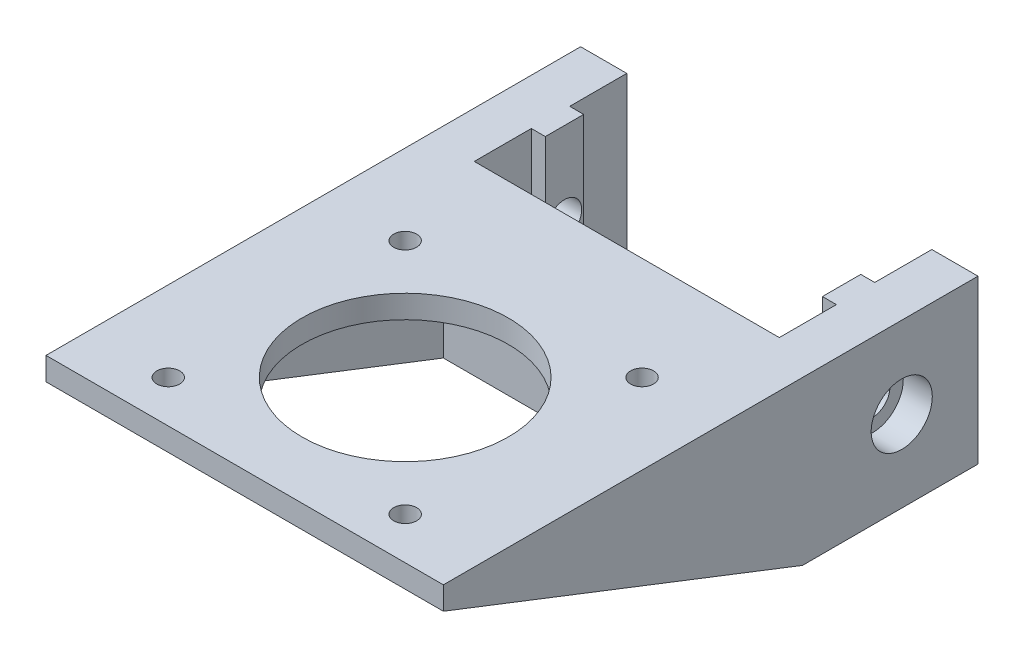
SolidWorks part; units mm, degrees
material "ABS"
ref_plane "Front Plane" through (0, 0, 0) normal (0, 0, 1) x (1, 0, 0)
ref_plane "Top Plane" through (0, 0, 0) normal (0, 1, 0) x (1, 0, 0)
ref_plane "Right Plane" through (0, 0, 0) normal (1, 0, 0) x (0, 0, -1)
sketch "Sketch1" plane through (0, 0, 0) normal (0, 0, 1) x (1, 0, 0)
  line L1 (77.1448, 157.566) -> (119.1448, 157.566)
  line L2 (77.1448, 157.566) -> (77.1448, 178.866)
  line L3 (77.1448, 178.866) -> (119.1448, 178.866)
  line L4 (119.1448, 157.566) -> (119.1448, 178.866)
  dimension "D1" = 42
  dimension "D2" = 21.3
extrude "Boss-Extrude1" add sketch "Sketch1" along normal blind 3
sketch "Sketch2" plane through (0, 0, 3) normal (0, 0, 1) x (1, 0, 0)
  line L0 (119.1448, 166.066) -> (77.1448, 166.066) construction
  line L1 (119.1448, 157.566) -> (119.1448, 178.866) construction
  line L2 (77.1448, 178.866) -> (77.1448, 157.566) construction
  line L3 (77.1448, 157.566) -> (119.1448, 157.566) construction
  circle A0 centre (108.6448, 166.066) radius 3
  circle A1 centre (88.6448, 166.066) radius 3
  dimension "D2" = 6
  dimension "D1" = 8.5
  dimension "D3" = 10.5
  dimension "D4" = 11.5
extrude "Cut-Extrude1" cut sketch "Sketch2" against normal blind 3
sketch "Sketch4" plane through (0, 178.866, 0) normal (0, 1, 0) x (-1, 0, 0)
  line L0 (-119.1448, 3) -> (-119.1448, 0) construction
  line L1 (-119.1448, 0) -> (-77.1448, 0)
  line L2 (-119.1448, 0) -> (-119.1448, 50)
  line L3 (-119.1448, 50) -> (-77.1448, 50)
  line L4 (-77.1448, 0) -> (-77.1448, 50)
  line L5 (-82.6448, 44.5002) -> (-113.6448, 44.5002) construction
  line L6 (-113.6448, 44.5002) -> (-113.6448, 13.5002) construction
  line L7 (-113.6448, 13.5002) -> (-82.6448, 13.5002) construction
  line L8 (-82.6448, 13.5002) -> (-82.6448, 44.5002) construction
  line L9 (-98.1448, 29.0002) -> (-98.1448, 13.5002) construction
  line L10 (-98.1448, 13.5002) -> (-98.1448, 0) construction
  circle A2 centre (-113.6448, 44.5002) radius 1.5
  circle A3 centre (-82.6448, 44.5002) radius 1.5
  circle A4 centre (-82.6448, 13.5002) radius 1.5
  circle A5 centre (-113.6448, 13.5002) radius 1.5
  circle A6 centre (-98.1448, 29.0002) radius 13.5
  point P9 (-119.1448, 50)
  dimension "D2" = 5.4998
  dimension "D7" = 3
  dimension "D8" = 27
  dimension "D1" = 50
  dimension "D4" = 15.5
  dimension "D5" = 31
  dimension "D6" = 31
extrude "Boss-Extrude2" add sketch "Sketch4" against normal blind 3
sketch "Sketch5" plane through (119.1448, 0, 0) normal (1, 0, 0) x (0, 0, -1)
  line L0 (0, 157.566) -> (0, 178.866)
  line L1 (0, 157.566) -> (0, 178.866) construction
  line L2 (0, 178.866) -> (-50, 178.866)
  line L4 (-50, 178.866) -> (0, 178.866) construction
  line L5 (-50, 178.866) -> (-50, 175.866)
  line L6 (-50, 175.866) -> (-3, 157.566)
  line L7 (-3, 157.566) -> (-3, 175.866) construction
  line L8 (-3, 157.566) -> (0, 157.566)
  line L9 (-50, 178.866) -> (0, 178.866) construction
extrude "Boss-Extrude3" add sketch "Sketch5" along normal blind 5
extrude "Boss-Extrude4" add sketch "Sketch5<3>" against normal blind 5 from offset 42 offset against normal yes
sketch "Sketch5<3>" plane through (119.1448, 0, 0) normal (1, 0, 0) x (0, 0, -1) same geometry as "Sketch5"
sketch "Sketch6" plane through (0, 178.866, 0) normal (0, 1, 0) x (1, 0, 0)
  line L0 (72.1448, 0) -> (72.1448, 19.96)
  line L2 (72.1448, 0) -> (72.1448, -50) construction
  line L3 (72.1448, 19.96) -> (78.1848, 19.96)
  line L4 (78.1848, 19.96) -> (78.1848, 0)
  line L5 (124.1448, 0) -> (72.1448, 0) construction
  line L6 (78.1848, 0) -> (72.1448, 0)
  dimension "D1" = 6.04
  dimension "D2" = 19.96
extrude "Boss-Extrude5" add sketch "Sketch6" against normal up to surface (21.3 mm away) up to face at (98.1448, 157.566, 2)
sketch "Sketch8" plane through (0, 157.566, 0) normal (0, -1, 0) x (-1, 0, 0)
  line L0 (-78.1848, 19.96) -> (-78.1848, 0) construction
  line L1 (-78.1848, 7.47) -> (-80.0148, 7.47)
  line L2 (-78.1848, 7.47) -> (-78.1848, 12.49)
  line L3 (-78.1848, 12.49) -> (-80.0148, 12.49)
  line L4 (-80.0148, 7.47) -> (-80.0148, 12.49)
extrude "Boss-Extrude6" add sketch "Sketch8" against normal up to surface (21.3 mm away) up to face at (95.3215, 178.866, 11.6767)
sketch "Sketch7" plane through (72.1448, 0, 0) normal (-1, 0, 0) x (0, 0, 1)
  line L0 (-9.98, 168.216) -> (-9.98, 178.866) construction
  line L1 (-19.96, 178.866) -> (50, 178.866) construction
  line L2 (-19.96, 157.566) -> (-19.96, 178.866) construction
  circle A0 centre (-9.98, 168.216) radius 2.25
  dimension "D1" = 4.5
  dimension "D2" = 9.98
  dimension "D3" = 10.65
extrude "Cut-Extrude2" cut sketch "Sketch7" against normal blind 10
ref_plane "Plane1" through (98.1448, 0, 0) normal (-1, 0, 0) x (0, 0, 1)
sketch "Sketch9" plane through (72.1448, 0, 0) normal (-1, 0, 0) x (0, 0, 1)
  circle A0 centre (-9.98, 168.216) radius 4
  dimension "D1" = 8
extrude "Cut-Extrude3" cut sketch "Sketch9" against normal blind 3.8
mirror "Mirror1" about plane through (98.1448, 0, 0) normal (-1, 0, 0) of "Cut-Extrude3", "Cut-Extrude2", "Boss-Extrude5", "Boss-Extrude6"
